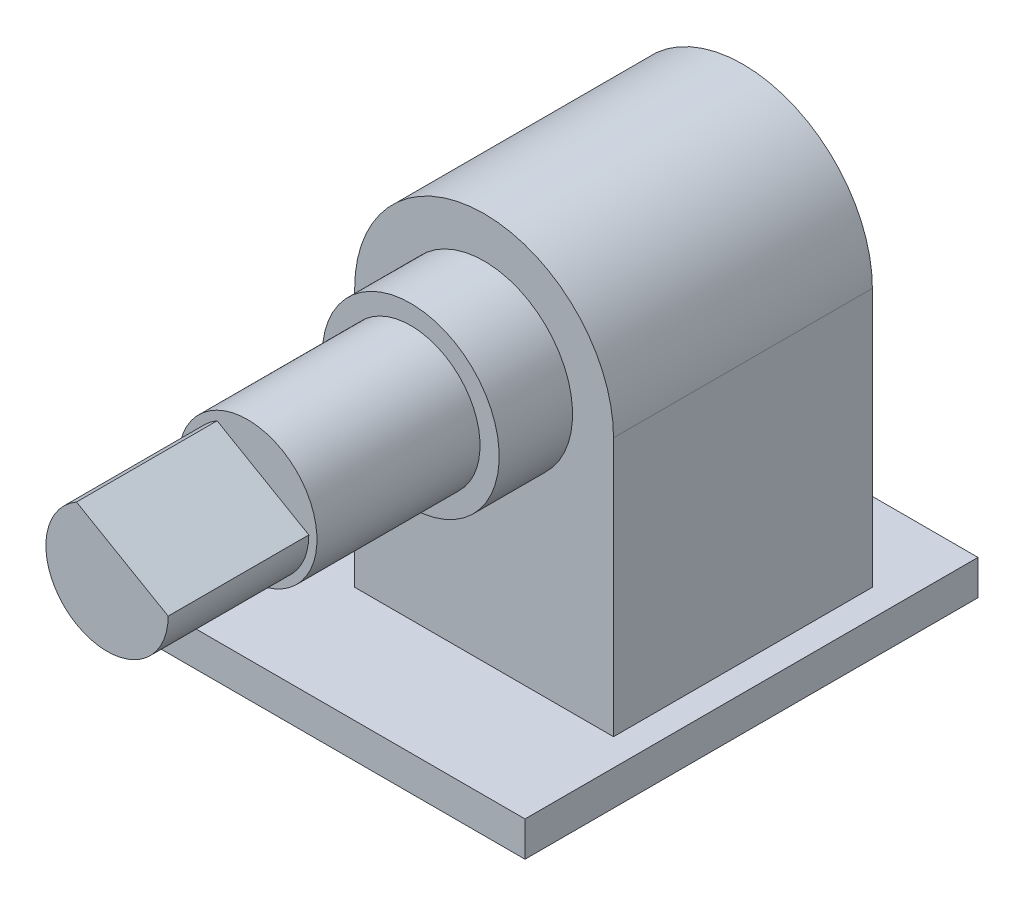
SolidWorks part; units mm, degrees
ref_plane "Front Plane" through (0, 0, 0) normal (0, 0, 1) x (1, 0, 0)
ref_plane "Top Plane" through (0, 0, 0) normal (0, 1, 0) x (1, 0, 0)
ref_plane "Right Plane" through (0, 0, 0) normal (1, 0, 0) x (0, 0, -1)
sketch "Sketch1" plane through (0, 0, 0) normal (0, 1, 0) x (1, 0, 0)
  line L1 (9.652, 11.1125) -> (-9.652, 11.1125)
  line L2 (9.652, 11.1125) -> (9.652, -11.1125)
  line L3 (9.652, -11.1125) -> (-9.652, -11.1125)
  line L4 (-9.652, 11.1125) -> (-9.652, -11.1125)
  line L5 (0, -11.1125) -> (0, 11.1125) construction
  line L6 (9.652, 0) -> (-9.652, 0) construction
  point P0 (0, 0)
  dimension "D1" = 22.225
  dimension "D2" = 19.304
extrude "Boss-Extrude1" add sketch "Sketch1" along normal blind 1.7145
sketch "Sketch2" plane through (0, 1.7145, 0) normal (0, 1, 0) x (1, 0, 0)
  line L0 (9.652, -11.1125) -> (9.652, 11.1125) construction
  line L1 (-4.3688, -5.4483) -> (8.3312, -5.4483)
  line L2 (-4.3688, -5.4483) -> (-4.3688, 7.2517)
  line L3 (-4.3688, 7.2517) -> (8.3312, 7.2517)
  line L4 (8.3312, -5.4483) -> (8.3312, 7.2517)
  line L5 (-4.3688, -5.4483) -> (8.3312, 7.2517) construction
  line L6 (-4.3688, 7.2517) -> (8.3312, -5.4483) construction
  line L7 (9.652, 11.1125) -> (-9.652, 11.1125) construction
  point P4 (1.9812, 0.9017)
  dimension "D1" = 12.7
  dimension "D2" = 12.7
  dimension "D3" = 1.3208
  dimension "D4" = 3.8608
extrude "Boss-Extrude2" add sketch "Sketch2" along normal blind 19.05
fillet "Fillet1" 2 edges at (8.3312, 20.7645, -0.9017) (-4.3688, 20.7645, -0.9017) type full round first side face at (8.3312, 11.2395, -0.9017) second side face at (-4.3688, 11.2395, -0.9017) middle face at (1.9812, 20.7645, -0.9017)
ref_plane "Plane1" through (0, 14.4145, 0) normal (0, 1, 0) x (1, 0, 0)
sketch "Sketch6" plane through (0, 14.4145, 0) normal (0, 1, 0) x (1, 0, 0)
  line L0 (1.9812, -5.4483) -> (1.9812, -23.9483) construction
  line L1 (-4.3688, -5.4483) -> (8.3312, -5.4483) construction
  line L2 (1.9812, -23.9483) -> (-1.0188, -23.9483)
  line L3 (-1.0188, -23.9483) -> (-1.0188, -17.0483)
  line L4 (-1.0188, -17.0483) -> (-1.4188, -17.0483)
  line L5 (-1.4188, -17.0483) -> (-1.4188, -9.0483)
  line L6 (-1.4188, -9.0483) -> (-2.3588, -9.0483)
  line L7 (-2.3588, -9.0483) -> (-2.3588, -5.4483)
  line L8 (-2.3588, -5.4483) -> (1.9812, -5.4483)
  line L9 (1.9812, -5.4483) -> (1.9812, -23.9483)
  dimension "D1" = 6
  dimension "D2" = 6.8
  dimension "D3" = 8.68
  dimension "D4" = 3.6
  dimension "D5" = 8
  dimension "D6" = 6.9
revolve "Revolve1" add sketch "Sketch6" angle 360 about L0
sketch "Sketch7" plane through (0, 0, 23.9483) normal (0, 0, 1) x (1, 0, 0)
  line L0 (0.4812, 17.0126) -> (4.9812, 14.4145)
  line L1 (2.7312, 15.7135) -> (0.4812, 11.8164) construction
  circle A2 centre (1.9812, 14.4145) radius 3 construction
  circle A3 centre (1.9812, 14.4145) radius 3 construction
  arc A4 (4.9812, 14.4145) -> (0.4812, 17.0126) centre (1.9812, 14.4145) ccw
  dimension "D1" = 30
  dimension "D2" = 4.5
extrude "Cut-Extrude1" cut sketch "Sketch7" against normal up to surface (6.9 mm away) up to face at (-1.0188, 14.4145, 17.0483)
